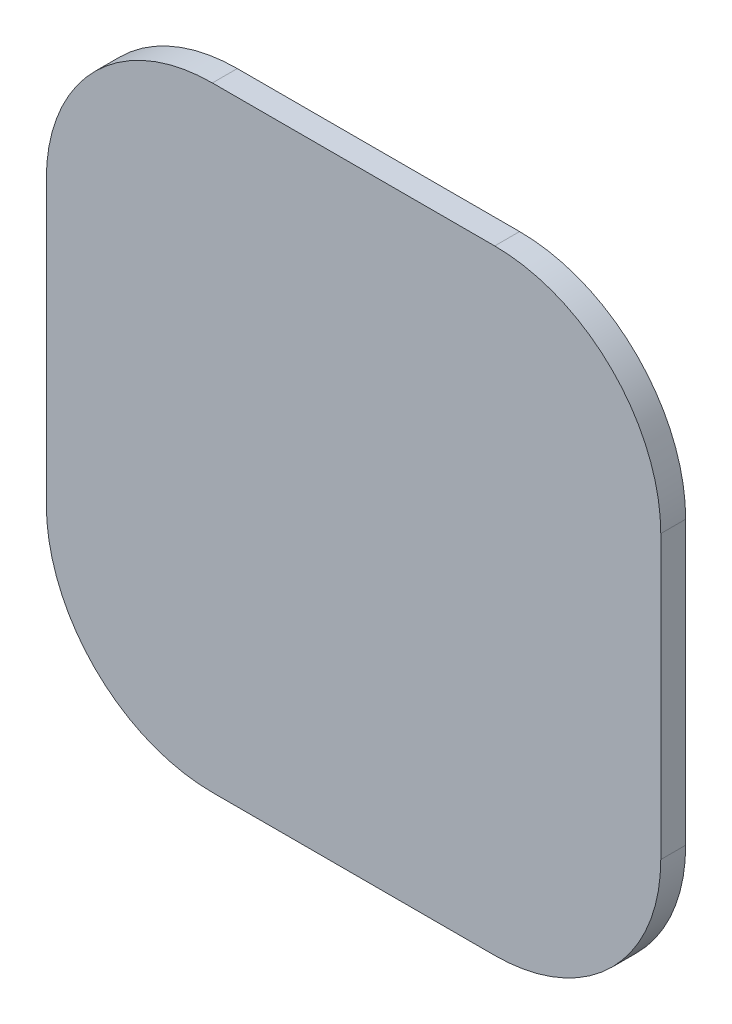
SolidWorks part; units mm, degrees
ref_plane "Front Plane" through (0, 0, 0) normal (0, 0, 1) x (1, 0, 0)
ref_plane "Top Plane" through (0, 0, 0) normal (0, 1, 0) x (1, 0, 0)
ref_plane "Right Plane" through (0, 0, 0) normal (1, 0, 0) x (0, 0, -1)
sketch "Эскиз1" plane through (0, 0, 0) normal (0, 0, 1) x (1, 0, 0)
  line L5 (-9.45, -27.55) -> (27.55, -27.55)
  line L6 (-9.45, -27.55) -> (-9.45, 9.45)
  line L7 (-9.45, 9.45) -> (27.55, 9.45)
  line L8 (27.55, -27.55) -> (27.55, 9.45)
  line L9 (-9.45, -27.55) -> (27.55, 9.45) construction
  line L10 (-9.45, 9.45) -> (27.55, -27.55) construction
  circle A0 centre (0, 0) radius 9.05
  circle A1 centre (18.1, 0) radius 9.05
  circle A2 centre (18.1, -18.1) radius 9.05
  circle A3 centre (0, -18.1) radius 9.05
  circle A4 centre (0, 0) radius 9
  circle A5 centre (18.1, 0) radius 9
  circle A6 centre (0, -18.1) radius 9
  circle A7 centre (18.1, -18.1) radius 9
  point P9 (0, 0)
  point P11 (9.05, -9.05)
  dimension "D1" = 18.1
  dimension "D2" = 37
  dimension "D3" = 0.05
  dimension "D4" = 0.05
  dimension "D5" = 0.05
  dimension "D6" = 0.05
extrude "Бобышка-Вытянуть1" add sketch "Эскиз1" along normal blind 1 contours L5 L8 L7 L6 A3 A0 A1 A2 | A0 | A3 | A1 | A2 | A3 A2 A1 A0 | A4 | A6 | A7 | A5 region at (-8.9267, -9.05, 0) region at (6.3812, -6.3812, 0) region at (9.05, -9.05, 0) region at (18.1, 9.0244, 0) region at (6.3812, -11.7188, 0) region at (24.4812, -11.7188, 0)
extrude "Бобышка-Вытянуть3" add sketch "Эскиз1<6>" against normal blind 0.5 contours L5 L8 L7 L6 A3 A0 A1 A2 | A3 A2 A1 A0 | A0 A4 | A1 A5 | A3 A6 region at (-8.9267, -9.05, 0) region at (6.3812, -6.3812, 0) region at (9.05, -9.05, 0) region at (18.1, 9.0244, 0) region at (6.3812, -11.7188, 0)
sketch "Эскиз1<6>" plane through (0, 0, 0) normal (0, 0, 1) x (1, 0, 0) same geometry as "Эскиз1"
fillet "Скругление1" radius 10 4 edges at (27.55, -27.55, 0.25) (27.55, 9.45, 0.25) (-9.45, 9.45, 0.25) (-9.45, -27.55, 0.25)
